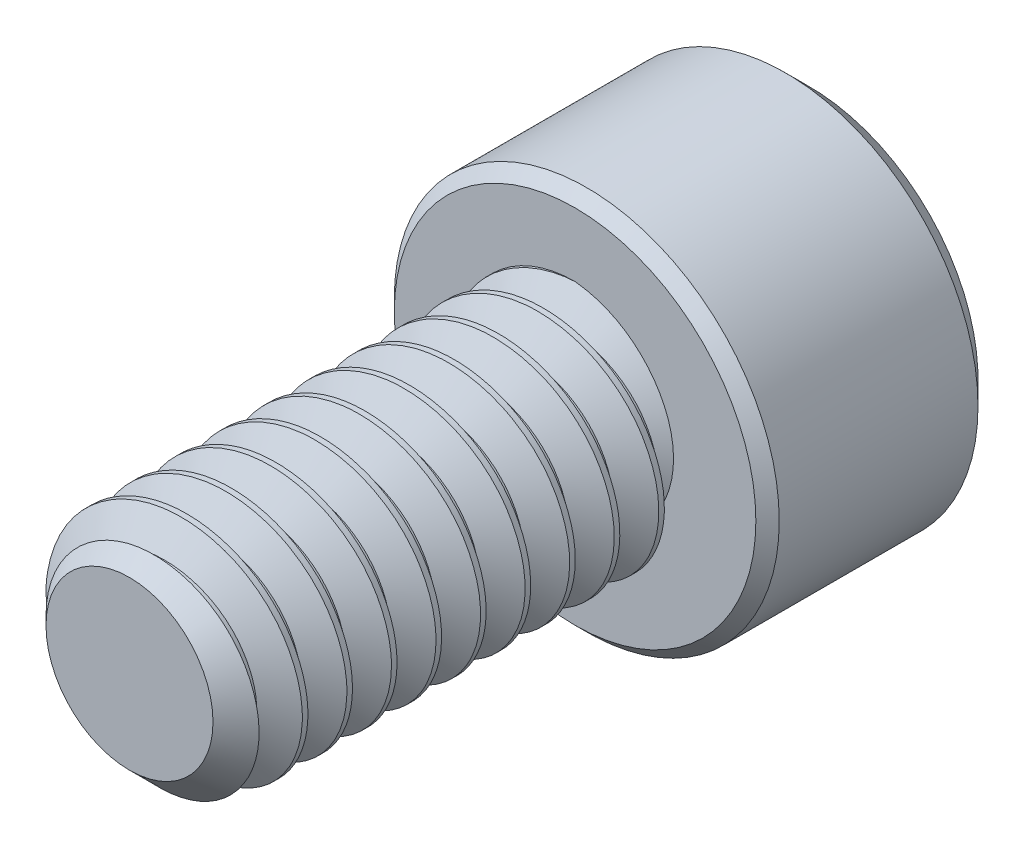
SolidWorks part; units mm, degrees
ref_plane "Front Plane" through (0, 0, 0) normal (0, 0, 1) x (1, 0, 0)
ref_plane "Top Plane" through (0, 0, 0) normal (0, 1, 0) x (1, 0, 0)
ref_plane "Right Plane" through (0, 0, 0) normal (1, 0, 0) x (0, 0, -1)
sketch "Sketch1" plane through (0, 0, 0) normal (0, 0, 1) x (1, 0, 0)
  line L0 (0, 2.0828) -> (0, -2.0828) construction
  circle A0 centre (0, 0) radius 2.0828
  dimension "OD" = 4.1656
extrude "Extrude1" add sketch "Sketch1" against normal blind 7.9375
sketch "Sketch2" plane through (0, 0, 0) normal (0, 0, 1) x (1, 0, 0)
  circle A0 centre (0, 0) radius 2.0828 construction
  circle A1 centre (0, 0) radius 2.0828
curve "Helix/Spiral1" pitch 0.7937 height 8.7312 turns 11 parameters "pitch"=0.7937
chamfer "Chamfer3" distance 0.5953 angle 45 1 edges at (2.0828, 0, 0)
sketch "Sketch3" plane through (0, 0, 0) normal (1, 0, 0) x (0, 0, -1)
  line L0 (-0.6945, 2.0828) -> (-0.3969, 1.5672)
  line L1 (-0.3969, 1.5672) -> (-0.2977, 1.5672)
  line L2 (-0.2977, 1.5672) -> (0, 2.0828)
  line L3 (-0.6945, 2.0828) -> (0, 2.0828)
  line L4 (-0.3473, 2.0828) -> (-0.3473, 1.5672) construction
  line L5 (-0.5457, 1.825) -> (-0.1488, 1.825) construction
  line L6 (0, 2.0828) -> (0, -2.0828) construction
  dimension "D1" = 0.0992
  dimension "D2" = 0.3969
  dimension "D3" = 60
sweep "Cut-Sweep1" cut profiles "Sketch3" path "Helix/Spiral1"
sketch "Sketch6" plane through (0, 0, -7.9375) normal (0, 0, -1) x (-1, 0, 0)
  circle A0 centre (0, 0) radius 3.429
  dimension "head dia" = 6.858
extrude "Extrude2" add sketch "Sketch6" along normal blind 4.1656
sketch "Sketch7" plane through (0, 0, -12.1031) normal (0, 0, -1) x (-1, 0, 0)
  line L1 (0, 2.0622) -> (-1.7859, 1.0311)
  line L2 (-1.7859, 1.0311) -> (-1.7859, -1.0311)
  line L3 (-1.7859, -1.0311) -> (0, -2.0622)
  line L4 (0, -2.0622) -> (1.7859, -1.0311)
  line L5 (1.7859, -1.0311) -> (1.7859, 1.0311)
  line L6 (1.7859, 1.0311) -> (0, 2.0622)
  circle A0 centre (0, 0) radius 1.7859 construction
  dimension "hex dia" = 3.5719
extrude "Cut-Extrude1" cut sketch "Sketch7" against normal blind 2.6789
sketch "Sketch8" plane through (0, 0, -12.1031) normal (0, 0, -1) x (-1, 0, 0)
  circle A0 centre (0, 0) radius 2.0622
extrude "Cut-Extrude2" cut sketch "Sketch8" against normal blind 0.4166 draft 45
chamfer "Chamfer1" distance 0.4166 angle 45 1 edges at (-3.429, 0, -12.1031)
chamfer "Chamfer2" distance 0.2083 angle 45 1 edges at (-3.429, 0, -7.9375)
sketch "Sketch9" plane through (0, 0, 0) normal (1, 0, 0) x (0, 0, -1)
  line L0 (0, 2.0828) -> (0, -2.0828) construction
  line L1 (4.3656, 2.0828) -> (4.3656, -2.0828) construction
  line L2 (7.9375, 3.429) -> (7.9375, -3.429) construction
  line L3 (12.1031, 3.429) -> (12.1031, -3.429) construction
  line L4 (12.1031, 0) -> (0, 0) construction
  dimension "D1" = 4.3656
  dimension "D2" = 4.1656
  dimension "D3" = 6.858
  dimension "D4" = 7.9375
equation "\"D3@Helix/Spiral1\" = \"screw length@Extrude1\"+\"pitch@Helix/Spiral1\""
equation "\"D1@Sketch3\" = \"pitch@Helix/Spiral1\"*.125"
equation "\"D2@Sketch3\" = \"pitch@Helix/Spiral1\"*.5"
equation "\"D1@Cut-Extrude1\" = \"hex dia@Sketch7\"*.75"
equation "\"D1@Chamfer1\" = \"head depth@Extrude2\"/10"
equation "\"D1@Sketch9\" = \"pitch@Helix/Spiral1\"*5.5"
equation "\"D1@Chamfer2\" = \"D1@Chamfer1\"/2"
equation "\"D1@Cut-Extrude2\" = \"D1@Chamfer2\"*2"
equation "\"D1@Chamfer3\" = \"pitch@Helix/Spiral1\"*.750"
equation "\"D2@Sketch9\" = \"head depth@Extrude2\""
equation "\"D3@Sketch9\" = \"head dia@Sketch6\""
equation "\"D4@Sketch9\" = \"screw length@Extrude1\""
